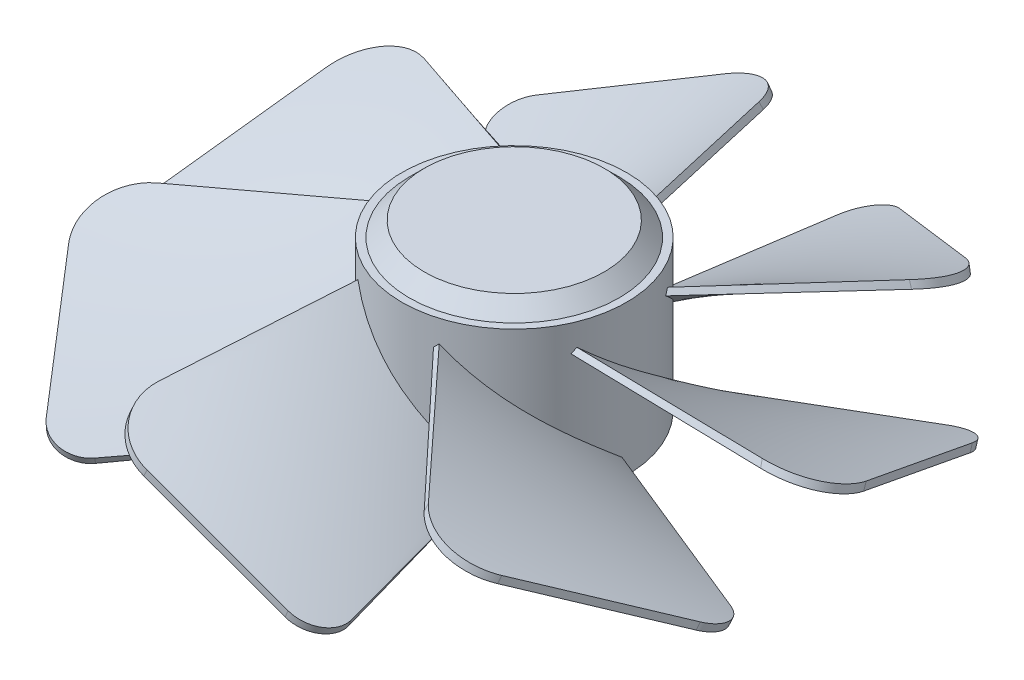
SolidWorks part; units mm, degrees
ref_plane "Front Plane" through (0, 0, 0) normal (0, 0, 1) x (1, 0, 0)
ref_plane "Top Plane" through (0, 0, 0) normal (0, 1, 0) x (1, 0, 0)
ref_plane "Right Plane" through (0, 0, 0) normal (1, 0, 0) x (0, 0, -1)
sketch "Sketch1" plane through (0, 0, 0) normal (0, 1, 0) x (1, 0, 0)
  circle A0 centre (0, 0) radius 15
extrude "Boss-Extrude1" add sketch "Sketch1" along normal blind 20
sketch "Sketch7" plane through (0, 0, 0) normal (0, 0, 1) x (1, 0, 0)
  line L0 (-7.211, 17.6634) -> (-6.571, 18.1434)
  line L1 (-7.211, 17.6634) -> (4.789, 1.6634)
  line L2 (-6.571, 18.1434) -> (5.429, 2.1434)
  line L3 (4.789, 1.6634) -> (5.429, 2.1434)
ref_plane "Plane1" through (0, 0, 43) normal (0, 0, 1) x (1, 0, 0)
sketch "Sketch8" plane through (0, 0, 43) normal (0, 0, 1) x (1, 0, 0)
  line L0 (-13.3487, 14.2867) -> (-13.6907, 13.347)
  line L1 (-13.3487, 14.2867) -> (17.6611, 3)
  line L2 (-13.6907, 13.347) -> (17.3191, 2.0604)
  line L3 (17.6611, 3) -> (17.3191, 2.0604)
  line L4 (-15, 0) -> (15, 0) construction
  dimension "D1" = 20
loft "Loft1" add profiles "Sketch7", "Sketch8"
pattern_circular "CirPattern1" count 7 over 360 about axis through (0, 20, 0) along (0, -1, 0) of "Loft1"
fillet "Fillet1" radius 7 7 edges
fillet "Fillet2" radius 4 7 edges
sketch "Sketch9" plane through (0, 20, 0) normal (0, 1, 0) x (1, 0, 0)
  circle A0 centre (0, 0) radius 12
extrude "Boss-Extrude2" add sketch "Sketch9" along normal blind 2
chamfer "Chamfer1" distance 2 angle 45 1 edges at (0, 20, 12)
sketch "Sketch10" plane through (0, 0, 0) normal (0, -1, 0) x (1, 0, 0)
  circle A0 centre (0, 0) radius 7
extrude "Cut-Extrude1" cut sketch "Sketch10" against normal blind 5
